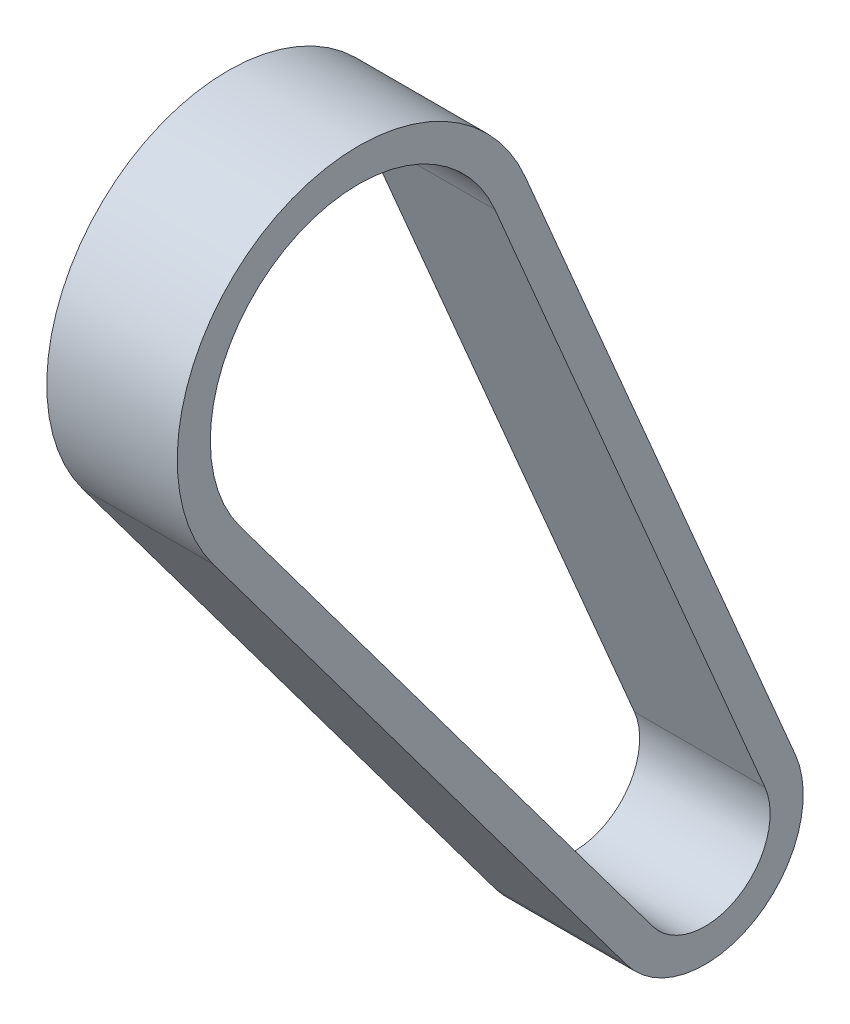
SolidWorks part; units mm, degrees
ref_plane "Alzado" through (0, 0, 0) normal (0, 0, 1) x (1, 0, 0)
ref_plane "Planta" through (0, 0, 0) normal (0, 1, 0) x (1, 0, 0)
ref_plane "Vista lateral" through (0, 0, 0) normal (1, 0, 0) x (0, 0, -1)
sketch "Croquis1" plane through (0, 0, 0) normal (0, 1, 0) x (1, 0, 0)
  line L1 (-101.6, -12.7) -> (101.6, -12.7)
  line L2 (-101.6, -12.7) -> (-101.6, 12.7)
  line L3 (-101.6, 12.7) -> (101.6, 12.7)
  line L4 (101.6, -12.7) -> (101.6, 12.7)
  line L5 (-101.6, -12.7) -> (101.6, 12.7) construction
  line L6 (-101.6, 12.7) -> (101.6, -12.7) construction
  point P0 (0, 0)
  dimension "D1" = 25.4
  dimension "D2" = 203.2
extrude "Saliente-Extruir1" add sketch "Croquis1" along normal blind 25.4
shell "Vaciado1" thickness 3.175 removed face at (-101.6, 12.7, 0) removed face at (101.6, 12.7, 0)
sketch "Croquis2" plane through (0, 25.4, 0) normal (0, 1, 0) x (1, 0, 0)
  line L0 (101.6, 12.7) -> (-101.6, 12.7) construction
  line L1 (-25.4, -12.7) -> (25.4, -12.7)
  line L2 (-25.4, -12.7) -> (-25.4, 12.7)
  line L3 (-25.4, 12.7) -> (25.4, 12.7)
  line L4 (25.4, -12.7) -> (25.4, 12.7)
  line L5 (-25.4, -12.7) -> (25.4, 12.7) construction
  line L6 (-25.4, 12.7) -> (25.4, -12.7) construction
  line L8 (-22.225, -9.525) -> (22.225, -9.525)
  line L9 (-22.225, -9.525) -> (-22.225, 9.525)
  line L10 (-22.225, 9.525) -> (22.225, 9.525)
  line L11 (22.225, -9.525) -> (22.225, 9.525)
  line L12 (-22.225, -9.525) -> (22.225, 9.525) construction
  line L13 (-22.225, 9.525) -> (22.225, -9.525) construction
  point P0 (0, 0)
  point P8 (0, 0)
  dimension "D1" = 50.8
  dimension "D2" = 3.175
  dimension "D3" = 3.175
extrude "Saliente-Extruir2" add sketch "Croquis2" along normal blind 247.65 separate body
sketch "Croquis3" plane through (0, 25.4, 0) normal (0, 1, 0) x (1, 0, 0)
  line L0 (0, 0) -> (0, 12.7) construction
  line L1 (25.4, 12.7) -> (-25.4, 12.7) construction
  circle A0 centre (-47.625, 0) radius 3.2639
  circle A1 centre (-79.375, 0) radius 3.2639
  circle A2 centre (79.375, 0) radius 3.2639
  circle A3 centre (47.625, 0) radius 3.2639
  dimension "D1" = 47.625
  dimension "D2" = 6.5278
  dimension "D3" = 31.75
extrude "Cortar-Extruir1" cut sketch "Croquis3" against normal through all
sketch "Croquis4" plane through (0, 0, 12.7) normal (0, 0, 1) x (1, 0, 0)
  line L0 (0, 25.4) -> (0, 139.6619) construction
  line L1 (-101.6, 25.4) -> (101.6, 25.4) construction
  line L2 (0, 139.6619) -> (-23.8125, 139.6619) construction
  circle A0 centre (0, 139.6619) radius 14.3129
  circle A1 centre (0, 139.6619) radius 23.8125 construction
  circle A2 centre (-23.8125, 139.6619) radius 2.4892 construction
  circle A3 centre (-11.9062, 160.2841) radius 2.4892
  circle A4 centre (11.9063, 160.2841) radius 2.4892
  circle A5 centre (23.8125, 139.6619) radius 2.4892 construction
  circle A6 centre (11.9062, 119.0397) radius 2.4892
  circle A7 centre (-11.9063, 119.0397) radius 2.4892
  dimension "D1" = 28.6258
  dimension "D3" = 47.625
  dimension "D4" = 4.9784
  dimension "D2" = 114.2619
  dimension "D6" = 23.8125
  dimension "D5" = 6
extrude "Cortar-Extruir2" cut sketch "Croquis4" against normal through all
sketch "Croquis8" plane through (0, 0, 12.7) normal (0, 0, 1) x (1, 0, 0)
  line L0 (0, 0) -> (0, 273.05) construction
  line L1 (-101.6, 12.7) -> (0, 12.7) construction
  line L2 (-101.6, 25.4) -> (-101.6, 0) construction
  line L3 (0, 12.7) -> (-12.7, 12.7) construction
  line L4 (0, 12.7) -> (12.7, 12.7) construction
  line L5 (-25.4, 273.05) -> (25.4, 273.05) construction
  line L6 (-12.7, 12.7) -> (-12.7, 25.4) construction
  circle A0 centre (0, 12.7) radius 2.4892
  circle A1 centre (-12.7, 12.7) radius 2.4892
  circle A2 centre (-25.4, 12.7) radius 2.4892
  circle A3 centre (-38.1, 12.7) radius 2.4892
  circle A4 centre (-50.8, 12.7) radius 2.4892
  circle A5 centre (0, 12.7) radius 2.4892
  circle A6 centre (-12.7, 12.7) radius 2.4892
  circle A7 centre (-25.4, 12.7) radius 2.4892
  circle A8 centre (-38.1, 12.7) radius 2.4892
  circle A9 centre (12.7, 12.7) radius 2.4892
  circle A10 centre (0, 12.7) radius 2.4892
  circle A11 centre (-12.7, 12.7) radius 2.4892
  circle A12 centre (-25.4, 12.7) radius 2.4892
  circle A13 centre (25.4, 12.7) radius 2.4892
  circle A14 centre (12.7, 12.7) radius 2.4892
  circle A15 centre (0, 12.7) radius 2.4892
  circle A16 centre (-12.7, 12.7) radius 2.4892
  circle A17 centre (38.1, 12.7) radius 2.4892
  circle A18 centre (25.4, 12.7) radius 2.4892
  circle A19 centre (12.7, 12.7) radius 2.4892
  circle A20 centre (0, 12.7) radius 2.4892
  circle A21 centre (12.7, 12.7) radius 2.4892
  circle A22 centre (25.4, 12.7) radius 2.4892
  circle A23 centre (38.1, 12.7) radius 2.4892
  circle A24 centre (50.8, 12.7) radius 2.4892
  circle A25 centre (-12.7, 25.4) radius 2.4892 [skipped]
  circle A26 centre (12.7, 25.4) radius 2.4892 [skipped]
  circle A27 centre (-12.7, 38.1) radius 2.4892
  circle A28 centre (12.7, 38.1) radius 2.4892
  circle A29 centre (-12.7, 50.8) radius 2.4892
  circle A30 centre (12.7, 50.8) radius 2.4892
  circle A31 centre (-12.7, 63.5) radius 2.4892
  circle A32 centre (12.7, 63.5) radius 2.4892
  circle A33 centre (-12.7, 76.2) radius 2.4892
  circle A34 centre (12.7, 76.2) radius 2.4892
  dimension "D1" = 4.9784
  dimension "D4" = 12.7
  dimension "D5" = 12.7
  dimension "D7" = 12.7
  dimension "D2" = 5
  dimension "D3" = 5
  dimension "D6" = 6
extrude "Cortar-Extruir4" cut sketch "Croquis8" against normal through all contours A4 | A3 | A2 | A1 | A0 | A9 | A13 | A17 | A24 | A28 | A29 | A30 | A31 | A32 | A34 | A33 | A27 region at (0, 12.7, 12.7) region at (-12.7, 12.7, 12.7) region at (-25.4, 12.7, 12.7) region at (-38.1, 12.7, 12.7) region at (-50.8, 12.7, 12.7) region at (12.7, 12.7, 12.7) region at (25.4, 12.7, 12.7) region at (38.1, 12.7, 12.7) region at (50.8, 12.7, 12.7) region at (12.7, 38.1, 12.7) region at (-12.7, 50.8, 12.7) region at (12.7, 50.8, 12.7) region at (-12.7, 63.5, 12.7) region at (12.7, 63.5, 12.7) region at (-12.7, 76.2, 12.7) region at (12.7, 76.2, 12.7)
sketch "Croquis6" plane through (0, 0, 12.7) normal (0, 0, 1) x (1, 0, 0)
  line L0 (25.4, 273.05) -> (25.4, 25.4) construction
  line L1 (-25.4, 88.646) -> (25.4, 88.646)
  line L2 (-25.4, 88.646) -> (-25.4, 114.046)
  line L3 (-25.4, 114.046) -> (25.4, 114.046)
  line L4 (25.4, 88.646) -> (25.4, 114.046)
  line L5 (-25.4, 88.646) -> (25.4, 114.046) construction
  line L6 (-25.4, 114.046) -> (25.4, 88.646) construction
  line L7 (-101.6, 25.4) -> (101.6, 25.4) construction
  line L9 (-22.225, 91.821) -> (22.225, 91.821)
  line L10 (-22.225, 91.821) -> (-22.225, 110.871)
  line L11 (-22.225, 110.871) -> (22.225, 110.871)
  line L12 (22.225, 91.821) -> (22.225, 110.871)
  line L13 (-22.225, 91.821) -> (22.225, 110.871) construction
  line L14 (-22.225, 110.871) -> (22.225, 91.821) construction
  point P0 (0, 101.346)
  point P11 (0, 101.346)
  dimension "D1" = 25.4
  dimension "D2" = 63.246
  dimension "D3" = 3.175
  dimension "D4" = 3.175
extrude "Saliente-Extruir3" add sketch "Croquis6" along normal blind 69.85 separate body
sketch "Croquis7" plane through (0, 114.046, 0) normal (0, 1, 0) x (1, 0, 0)
  line L0 (0, -12.7) -> (0, -82.55) construction
  line L1 (-25.4, -12.7) -> (25.4, -12.7) construction
  line L2 (25.4, -82.55) -> (-25.4, -82.55) construction
  line L3 (16.51, -12.7) -> (-16.51, -12.7)
  line L4 (25.4, -12.7) -> (-25.4, -12.7) construction
  line L5 (-16.51, -12.7) -> (-16.51, -34.798)
  line L6 (-13.208, -38.1) -> (13.208, -38.1)
  line L7 (16.51, -12.7) -> (16.51, -34.798)
  arc A0 (16.51, -34.798) -> (13.208, -38.1) centre (13.208, -34.798) cw
  arc A1 (-16.51, -34.798) -> (-13.208, -38.1) centre (-13.208, -34.798) ccw
  point P12 (0, -38.1)
  point P16 (16.51, -38.1)
  point P19 (-16.51, -38.1)
  dimension "D3" = 3.302
  dimension "D1" = 25.4
  dimension "D2" = 33.02
extrude "Cortar-Extruir3" cut sketch "Croquis7" against normal up to next (3.175 mm away)
sketch "Croquis11" plane through (25.4, 0, 0) normal (1, 0, 0) x (0, 0, -1)
  line L0 (0, -101.854) -> (-381, -101.854) construction
  line L1 (-82.55, 88.646) -> (-82.55, 114.046) construction
  line L2 (-82.55, 88.646) -> (-12.7, 88.646) construction
  line L6 (-517.96, -101.854) -> (-276.66, -101.854) construction
  line L7 (-517.96, -101.854) -> (-517.96, 139.446) construction
  line L8 (-517.96, 139.446) -> (-276.66, 139.446) construction
  line L9 (-276.66, -101.854) -> (-276.66, 139.446) construction
  circle A0 centre (-396.875, 145.796) radius 38.1
  dimension "D3" = 76.2
  dimension "D4" = 209.55
  dimension "D5" = 276.225
  dimension "D1" = 190.5
  dimension "D2" = 381
  dimension "D6" = 241.3
sketch "Croquis9" plane through (0, 0, 12.7) normal (0, 0, 1) x (1, 0, 0)
  line L0 (0, 0) -> (0, 273.05) construction
  line L1 (-25.4, 273.05) -> (25.4, 273.05) construction
  line L2 (50.8, 0) -> (-50.8, 0)
  line L3 (-101.6, 0) -> (101.6, 0) construction
  line L4 (-57.15, 6.35) -> (-57.15, 23.7481)
  line L5 (-101.6, 25.4) -> (101.6, 25.4) construction
  line L6 (-56.3451, 26.8425) -> (-27.2168, 79.0403)
  line L7 (-25.4, 273.05) -> (-25.4, 25.4) construction
  line L8 (-21.6717, 82.296) -> (21.6717, 82.296)
  line L9 (56.3451, 26.8425) -> (27.2168, 79.0403)
  line L10 (57.15, 6.35) -> (57.15, 23.7481)
  line L11 (-25.4, 88.646) -> (25.4, 88.646) construction
  circle A0 centre (-50.8, 12.7) radius 2.4892 construction
  arc A2 (-50.8, 0) -> (-57.15, 6.35) centre (-50.8, 6.35) cw
  arc A3 (-57.15, 23.7481) -> (-56.3451, 26.8425) centre (-50.8, 23.7481) cw
  arc A4 (-27.2168, 79.0403) -> (-21.6717, 82.296) centre (-21.6717, 75.946) cw
  arc A5 (27.2168, 79.0403) -> (21.6717, 82.296) centre (21.6717, 75.946) ccw
  arc A6 (57.15, 23.7481) -> (56.3451, 26.8425) centre (50.8, 23.7481) ccw
  arc A7 (50.8, 0) -> (57.15, 6.35) centre (50.8, 6.35) ccw
  circle A9 centre (-25.4, 12.7) radius 2.4892
  circle A10 centre (-25.4, 12.7) radius 2.4892
  circle A11 centre (-12.7, 12.7) radius 2.4892
  circle A12 centre (-12.7, 12.7) radius 2.4892
  circle A13 centre (0, 12.7) radius 2.4892
  circle A14 centre (0, 12.7) radius 2.4892
  circle A15 centre (0, 12.7) radius 2.4892
  circle A16 centre (0, 12.7) radius 2.4892
  circle A17 centre (12.7, 12.7) radius 2.4892
  circle A18 centre (12.7, 12.7) radius 2.4892
  circle A19 centre (-38.1, 12.7) radius 2.4892
  circle A20 centre (-38.1, 12.7) radius 2.4892
  circle A21 centre (-25.4, 12.7) radius 2.4892
  circle A22 centre (-25.4, 12.7) radius 2.4892
  circle A23 centre (-12.7, 12.7) radius 2.4892
  circle A24 centre (-12.7, 12.7) radius 2.4892
  circle A25 centre (0, 12.7) radius 2.4892
  circle A26 centre (0, 12.7) radius 2.4892
  circle A27 centre (-50.8, 12.7) radius 2.4892
  circle A28 centre (-50.8, 12.7) radius 2.4892
  circle A29 centre (-38.1, 12.7) radius 2.4892
  circle A30 centre (-38.1, 12.7) radius 2.4892
  circle A31 centre (25.4, 12.7) radius 2.4892
  circle A32 centre (25.4, 12.7) radius 2.4892
  circle A33 centre (38.1, 12.7) radius 2.4892
  circle A34 centre (38.1, 12.7) radius 2.4892
  circle A35 centre (-12.7, 12.7) radius 2.4892
  circle A36 centre (-12.7, 12.7) radius 2.4892
  circle A37 centre (0, 12.7) radius 2.4892
  circle A38 centre (0, 12.7) radius 2.4892
  circle A39 centre (12.7, 12.7) radius 2.4892
  circle A40 centre (12.7, 12.7) radius 2.4892
  circle A41 centre (25.4, 12.7) radius 2.4892
  circle A42 centre (25.4, 12.7) radius 2.4892
  circle A43 centre (-25.4, 12.7) radius 2.4892
  circle A44 centre (-25.4, 12.7) radius 2.4892
  circle A45 centre (-12.7, 12.7) radius 2.4892
  circle A46 centre (-12.7, 12.7) radius 2.4892
  circle A47 centre (50.8, 12.7) radius 2.4892
  circle A48 centre (50.8, 12.7) radius 2.4892
  circle A49 centre (38.1, 12.7) radius 2.4892
  circle A50 centre (38.1, 12.7) radius 2.4892
  circle A51 centre (25.4, 12.7) radius 2.4892
  circle A52 centre (25.4, 12.7) radius 2.4892
  circle A53 centre (12.7, 12.7) radius 2.4892
  circle A54 centre (12.7, 12.7) radius 2.4892
  circle A55 centre (0, 12.7) radius 2.4892
  circle A56 centre (0, 12.7) radius 2.4892
  circle A57 centre (12.7, 12.7) radius 2.4892
  circle A58 centre (12.7, 12.7) radius 2.4892
  circle A59 centre (-12.7, 76.2) radius 2.4892
  circle A60 centre (-12.7, 76.2) radius 2.4892
  circle A61 centre (12.7, 63.5) radius 2.4892
  circle A62 centre (12.7, 63.5) radius 2.4892
  circle A63 centre (-12.7, 63.5) radius 2.4892
  circle A64 centre (-12.7, 63.5) radius 2.4892
  circle A65 centre (12.7, 50.8) radius 2.4892
  circle A66 centre (12.7, 50.8) radius 2.4892
  circle A67 centre (-12.7, 50.8) radius 2.4892
  circle A68 centre (-12.7, 50.8) radius 2.4892
  circle A69 centre (12.7, 38.1) radius 2.4892
  circle A70 centre (12.7, 38.1) radius 2.4892
  circle A71 centre (-12.7, 38.1) radius 2.4892
  circle A72 centre (-12.7, 38.1) radius 2.4892
  circle A73 centre (12.7, 76.2) radius 2.4892
  circle A74 centre (12.7, 76.2) radius 2.4892
  point P22 (-57.15, 0)
  point P25 (-57.15, 25.4)
  point P28 (-25.4, 82.296)
  point P38 (0, 82.296)
  circle M37 centre (-50.8, 12.7) radius 2.4892
  circle M38 centre (-38.1, 12.7) radius 2.4892
  circle M39 centre (-25.4, 12.7) radius 2.4892
  circle M40 centre (-12.7, 12.7) radius 2.4892
  circle M41 centre (0, 12.7) radius 2.4892
  circle M42 centre (12.7, 12.7) radius 2.4892
  circle M43 centre (25.4, 12.7) radius 2.4892
  circle M44 centre (38.1, 12.7) radius 2.4892
  circle M45 centre (50.8, 12.7) radius 2.4892
  line M46 (-101.6, 0) -> (101.6, 0)
  line M48 (101.6, 25.4) -> (-101.6, 25.4)
  dimension "D1" = 6.35
  dimension "D3" = 6.35
  dimension "D37" = 6.35
  dimension "D4" = 0
  dimension "D5" = 0
  dimension "D6" = 0
  dimension "D7" = 0
  dimension "D8" = 0
  dimension "D9" = 0
  dimension "D10" = 0
  dimension "D11" = 0
  dimension "D12" = 0
  dimension "D13" = 0
  dimension "D14" = 0
  dimension "D15" = 0
  dimension "D16" = 0
  dimension "D17" = 0
  dimension "D18" = 0
  dimension "D19" = 0
  dimension "D20" = 0
  dimension "D21" = 0
  dimension "D22" = 0
  dimension "D23" = 0
  dimension "D24" = 0
  dimension "D25" = 0
  dimension "D26" = 0
  dimension "D27" = 0
  dimension "D28" = 0
  dimension "D29" = 0
  dimension "D30" = 0
  dimension "D31" = 0
  dimension "D32" = 0
  dimension "D33" = 0
  dimension "D34" = 0
  dimension "D35" = 0
  dimension "D36" = 0
extrude "Saliente-Extruir4" add sketch "Croquis9" along normal blind 6.35 separate body contours L0 L8 A4 L6 A3 A60 A64 A68 A72 M48 | L0 A6 L9 A5 L8 A74 A70 A66 A62 M48 | L0 A3 L4 A2 M46 M41 M48 M37 M39 M40 M38 | L0 L2 A7 L10 A6 A56 M48 M42 M44 M45 M43 region at (-28.4143, 12.7709, 12.7) region at (28.4143, 12.7709, 12.7) region at (-21.9575, 49.932, 12.7) region at (21.9575, 49.932, 12.7)
sketch "Croquis15" plane through (25.4, 0, 0) normal (1, 0, 0) x (0, 0, -1)
  line L0 (-12.7, 0) -> (-12.7, 171.1325) construction
  line L1 (-12.7, 273.05) -> (-12.7, 25.4) construction
  line L2 (-72.5746, 227.1642) -> (-41.5317, 154.1315) construction
  line L3 (-105.4538, 208.2656) -> (-57.9713, 144.6822) construction
  line L4 (-94.6246, 238.2605) -> (-401.3483, 164.3633) construction
  line L5 (-392.4017, 127.2287) -> (-85.6779, 201.1258) construction
  line L8 (-82.55, 114.046) -> (-12.7, 114.046) construction
  circle A0 centre (-50.32, 150.396) radius 30
  arc A1 (-57.9713, 144.6822) -> (-41.5317, 154.1315) centre (-50.32, 150.396) ccw construction
  arc A2 (-401.3483, 164.3633) -> (-392.4017, 127.2287) centre (-396.875, 145.796) ccw construction
  arc A3 (-72.5746, 227.1642) -> (-105.4538, 208.2656) centre (-90.1513, 219.6932) ccw construction
  arc A4 (-85.6779, 201.1258) -> (-94.6246, 238.2605) centre (-90.1513, 219.6932) ccw construction
  dimension "D2" = 60
  dimension "D3" = 19.0986
  dimension "D4" = 38.1972
  dimension "D1" = 171.1325
  dimension "D7" = 6.35
  dimension "D8" = 7.62
sketch "Croquis16" plane through (25.4, 0, 0) normal (1, 0, 0) x (0, 0, -1)
  line L0 (-50.32, 150.396) -> (-50.32, 175.796) construction
  line L1 (-13.4332, 272.8734) -> (-118.1525, 247.644)
  line L2 (-82.55, 94.996) -> (-82.55, 113.9625)
  line L3 (-82.5522, 114.1295) -> (-83.4835, 149.5234)
  line L4 (-76.2, 88.646) -> (6.35, 88.646)
  line L5 (12.7, 273.05) -> (12.7, 25.4) construction
  line L6 (12.7, 94.996) -> (12.7, 266.7)
  line L7 (6.35, 273.05) -> (-11.9459, 273.05)
  line L8 (-94.6246, 238.2605) -> (-401.3483, 164.3633) construction
  line L9 (-122.8385, 239.9833) -> (-110.0117, 186.743)
  line L10 (-90.1513, 219.6932) -> (-116.4251, 213.3632) construction
  circle A0 centre (-90.1513, 219.6932) radius 14.3256
  circle A1 centre (-50.32, 150.396) radius 33.175
  circle A4 centre (-50.32, 150.396) radius 9.5631
  circle A5 centre (-50.32, 150.396) radius 25.4 construction
  circle A6 centre (-50.32, 175.796) radius 2.4892
  circle A7 centre (-32.3595, 168.3565) radius 2.4892 construction
  circle A8 centre (-24.92, 150.396) radius 2.4892
  circle A9 centre (-32.3595, 132.4355) radius 2.4892
  circle A10 centre (-50.32, 124.996) radius 2.4892
  circle A11 centre (-68.2805, 132.4355) radius 2.4892
  circle A12 centre (-75.72, 150.396) radius 2.4892
  circle A13 centre (-68.2805, 168.3565) radius 2.4892
  arc A18 (-105.7366, 182.1707) -> (-83.4864, 151.1506) centre (-115.2282, 151.8727) cw
  arc A19 (-110.0117, 186.743) -> (-105.7366, 182.1707) centre (-103.8383, 188.2304) ccw
  arc A21 (-118.1525, 247.644) -> (-122.8385, 239.9833) centre (-116.6652, 241.4706) ccw
  arc A23 (-11.9459, 273.05) -> (-13.4332, 272.8734) centre (-11.9459, 266.7) ccw
  circle A26 centre (-50.32, 150.396) radius 30 construction
  arc A29 (-82.55, 113.9625) -> (-82.5522, 114.1295) centre (-88.9, 113.9625) ccw
  arc A31 (12.7, 266.7) -> (6.35, 273.05) centre (6.35, 266.7) ccw
  arc A32 (6.35, 88.646) -> (12.7, 94.996) centre (6.35, 94.996) ccw
  arc A33 (-82.55, 94.996) -> (-76.2, 88.646) centre (-76.2, 94.996) ccw
  point P45 (-12.7, 273.05)
  point P72 (-82.55, 114.046)
  point P74 (12.7, 273.05)
  point P77 (12.7, 88.646)
  point P80 (-82.55, 88.646)
  line M2 (12.7, 25.4) -> (12.7, 273.05)
  line M3 (12.7, 273.05) -> (-12.7, 273.05)
  line M4 (-12.7, 273.05) -> (-12.7, 25.4)
  dimension "D1" = 28.6512
  dimension "D2" = 3.175
  dimension "D3" = 31.75
  dimension "D4" = 19.1262
  dimension "D5" = 50.8
  dimension "D6" = 4.9784
  dimension "D9" = 6.35
  dimension "D10" = 6.35
  dimension "D14" = 6.35
  dimension "D15" = 6.35
  dimension "D12" = 6.35
  dimension "D8" = 25.4
  dimension "D11" = 12.7
  dimension "D7" = 8
extrude "Saliente-Extruir5" add sketch "Croquis16" along normal blind 6.35 separate body contours L4 A32 A31 A23 M2 M3 M4 | L2 A33 L4 A23 L1 A21 L9 A19 A18 A1 L3 A29 A0 M4 | A1 A13 A12 A11 A10 A9 A8 A6 A4 region at (25.4, 191.9467, 55.8371) region at (25.4, 180.8478, 0.0418) region at (25.4, 182.6306, 49.9534)
sketch "Croquis12" plane through (25.4, 0, 0) normal (1, 0, 0) x (0, 0, -1)
  line L0 (-82.55, 101.346) -> (-12.7, 101.346) construction
  line L1 (-82.55, 88.646) -> (-82.55, 114.046) construction
  line L2 (-12.7, 88.646) -> (-12.7, 114.046) construction
  line L3 (0, 273.05) -> (0, 0) construction
  line L4 (-12.7, 273.05) -> (12.7, 273.05) construction
  line L5 (0, 101.346) -> (-12.7, 101.346) construction
  line L6 (0, 101.346) -> (0, 114.046) construction
  circle A1 centre (0, 101.346) radius 2.4892
  circle A2 centre (-12.7, 101.346) radius 2.4892 [skipped]
  circle A3 centre (-25.4, 101.346) radius 2.4892
  circle A4 centre (-38.1, 101.346) radius 2.4892
  circle A5 centre (-50.8, 101.346) radius 2.4892
  circle A6 centre (0, 114.046) radius 2.4892
  circle A7 centre (0, 126.746) radius 2.4892
  circle A8 centre (0, 139.446) radius 2.4892
  circle A9 centre (0, 152.146) radius 2.4892
  circle A10 centre (0, 164.846) radius 2.4892
  circle A11 centre (0, 177.546) radius 2.4892
  circle A12 centre (0, 190.246) radius 2.4892
  circle A13 centre (0, 202.946) radius 2.4892
  circle A14 centre (0, 215.646) radius 2.4892
  circle A15 centre (0, 228.346) radius 2.4892
  circle A16 centre (0, 241.046) radius 2.4892
  circle A17 centre (0, 253.746) radius 2.4892
  circle A18 centre (0, 266.446) radius 2.4892
  circle A19 centre (-63.5, 101.346) radius 2.4892
  circle A20 centre (-76.2, 101.346) radius 2.4892
  dimension "D1" = 4.9784
  dimension "D3" = 12.7
  dimension "D5" = 12.7
  dimension "D2" = 7
  dimension "D4" = 14
extrude "Cortar-Extruir5" cut sketch "Croquis12" against normal through all and the other way through all
sketch "Croquis17" plane through (31.75, 0, 0) normal (1, 0, 0) x (0, 0, -1)
  line L0 (-403.5186, 170.3118) -> (-118.2389, 247.6205)
  line L1 (-118.0654, 247.6649) -> (-21.2705, 270.9852)
  line L2 (-390.9258, 121.1026) -> (-118.1525, 186.8202)
  line L3 (-392.4017, 127.2287) -> (-85.6779, 201.1258) construction
  line L4 (-118.1525, 186.8202) -> (-112.4025, 188.2055)
  line L5 (-13.4332, 206.3797) -> (-13.4332, 264.8118)
  line L7 (-403.3993, 184.1476) -> (-418.6226, 158.9186)
  circle A0 centre (-396.875, 145.796) radius 14.3256
  circle A1 centre (-90.1513, 219.6932) radius 14.3256
  circle A2 centre (-396.875, 145.796) radius 25.4
  arc A3 (-118.2389, 247.6205) -> (-118.0654, 247.6649) centre (-116.578, 241.4916) cw
  arc A4 (-21.2705, 270.9852) -> (-13.4332, 264.8118) centre (-19.7832, 264.8118) cw
  arc A5 (-13.4332, 206.3797) -> (-43.9384, 181.4981) centre (-38.8332, 206.3797) cw
  circle A6 centre (-50.32, 150.396) radius 31.75
  arc A8 (-110.0117, 186.743) -> (-105.7366, 182.1707) centre (-103.8383, 188.2304) ccw construction
  arc A9 (-110.0117, 186.743) -> (-105.7366, 182.1707) centre (-103.8383, 188.2304) ccw
  arc A10 (-110.0117, 186.743) -> (-112.4025, 188.2055) centre (-111.9383, 186.2789) ccw
  arc A11 (-83.4864, 151.1506) -> (-105.7366, 182.1707) centre (-115.2282, 151.8727) ccw construction
  arc A12 (-89.8175, 170.9084) -> (-105.7366, 182.1707) centre (-115.2282, 151.8727) ccw
  arc A13 (-89.8175, 170.9084) -> (-74.8387, 170.5677) centre (-82.1943, 176.6192) ccw
  circle A14 centre (-396.875, 180.2108) radius 7.62
  arc A16 (-389.8471, 183.1558) -> (-377.8191, 177.2761) centre (-380.4766, 187.0824) ccw
  point P19 (-118.1525, 247.644)
  point P23 (-13.4332, 272.8734)
  line M28 (-13.4332, 272.8734) -> (-118.1525, 247.644)
  arc M29 (-118.1525, 247.644) -> (-122.8385, 239.9833) centre (-116.6652, 241.4706) ccw
  line M30 (-122.8385, 239.9833) -> (-110.0117, 186.743)
  circle M38 centre (-90.1513, 219.6932) radius 14.3256
  dimension "D1" = 28.6512
  dimension "D2" = 50.8
  dimension "D3" = 6.35
  dimension "D4" = 63.5
  dimension "D5" = 9.525
  dimension "D6" = 25.4
  dimension "D7" = 15.24
  dimension "D8" = 34.4148
  dimension "D9" = 10.16
extrude "Saliente-Extruir6" add sketch "Croquis17" along normal blind 6.35 separate body contours A2 L2 L0 M30 M29 | L5 A4 A3 L0 M28 M29 M30 M38 | A2 A0 | A16 A14 L7 A2 L0 | A14 M30 region at (31.75, 173.536, 401.4081) region at (31.75, 184.8147, 244.5216) region at (31.75, 165.3985, 381.8776) region at (31.75, 220.7032, 61.6214) region at (31.75, 180.2108, 396.875)
sketch "Croquis18" plane through (38.1, 0, 0) normal (1, 0, 0) x (0, 0, -1)
  line L0 (-122.8385, 239.9833) -> (-110.0117, 186.743) construction
  line L1 (-122.754, 239.6323) -> (-111.9631, 194.8431)
  line L2 (-403.5186, 170.3118) -> (-118.2389, 247.6205) construction
  line L3 (-403.3993, 184.1476) -> (-418.6226, 158.9186) construction
  line L5 (-403.3993, 184.1476) -> (-418.6226, 158.9186)
  line L6 (-390.9258, 121.1026) -> (-118.1525, 186.8202) construction
  line L7 (-403.5186, 170.3118) -> (-130.5882, 244.274)
  line L10 (-122.8385, 239.9833) -> (-110.0117, 186.743) construction
  line L11 (-390.9258, 121.1026) -> (-116.6492, 187.1824)
  circle A1 centre (-396.875, 145.796) radius 25.4
  circle A2 centre (-396.875, 145.796) radius 25.4
  arc A3 (-116.6492, 187.1824) -> (-111.9631, 194.8431) centre (-118.1365, 193.3558) ccw
  circle A5 centre (-396.875, 145.796) radius 14.3256
  circle A6 centre (-396.875, 145.796) radius 14.3256
  arc A12 (-122.754, 239.6323) -> (-130.5882, 244.274) centre (-128.9273, 238.145) ccw
  arc A13 (-389.8471, 183.1558) -> (-377.8191, 177.2761) centre (-380.4766, 187.0824) ccw construction
  circle A14 centre (-396.875, 180.2108) radius 7.62 construction
  arc A15 (-389.8471, 183.1558) -> (-377.8191, 177.2761) centre (-380.4766, 187.0824) ccw
  circle A16 centre (-396.875, 180.2108) radius 7.62
  point P18 (-110.4758, 188.6697)
  line M10 (-118.2389, 247.6205) -> (-377.8191, 177.2761)
  arc M11 (-418.6226, 158.9186) -> (-390.9258, 121.1026) centre (-396.875, 145.796) ccw
  circle M13 centre (-396.875, 145.796) radius 14.3256
  line M33 (-403.3993, 184.1476) -> (-418.6226, 158.9186)
  arc M34 (-377.8191, 177.2761) -> (-389.8471, 183.1558) centre (-380.4766, 187.0824) cw
  arc M35 (-389.8471, 183.1558) -> (-403.3993, 184.1476) centre (-396.875, 180.2108) ccw
  dimension "D2" = 6.35
  dimension "D1" = 0
  dimension "D3" = 0
extrude "Saliente-Extruir7" add sketch "Croquis18" along normal blind 6.35 from surface separate body contours L1 A12 A2 A3 M10 | A2 M11 M13 | A16 A2 L7 M33 M34 | A16 M35 region at (38.1, 184.7417, 244.7476) region at (38.1, 173.536, 401.4081) region at (38.1, 131.2122, 416.7871) region at (38.1, 180.2108, 396.875) starting at face at (25.4, 101.346, -2.4892)
sketch "Croquis22" plane through (38.1, 0, 0) normal (1, 0, 0) x (0, 0, -1)
  line L0 (-396.875, 145.796) -> (-90.1513, 219.6932) construction
  line L1 (-90.1513, 219.6932) -> (-50.32, 150.396) construction
  line L4 (-50.32, 236.121) -> (-37.62, 236.121) construction
  line L5 (-21.2705, 270.9852) -> (-118.0654, 247.6649) construction
  circle A0 centre (-396.875, 180.2108) radius 3.2639
  circle A1 centre (-364.7735, 153.53) radius 3.2639
  circle A2 centre (-396.875, 145.796) radius 19.0986 construction
  arc A3 (-401.3483, 164.3633) -> (-392.4017, 127.2287) centre (-396.875, 145.796) ccw construction
  circle A4 centre (-364.7735, 153.53) radius 6.35 construction
  circle A7 centre (-72.747, 189.4137) radius 3.2639
  circle A8 centre (-72.747, 189.4137) radius 6.35 construction
  circle A9 centre (-50.32, 213.896) radius 6.35 construction
  circle A10 centre (-50.32, 213.896) radius 3.2639
  circle A13 centre (-37.62, 236.121) radius 3.2639
  circle A14 centre (-37.62, 236.121) radius 6.35 construction
  circle A15 centre (-72.747, 252.0515) radius 3.2639
  circle A16 centre (-72.747, 252.0515) radius 6.35 construction
  circle A17 centre (-19.7832, 264.8118) radius 6.35 construction
  circle A18 centre (-19.7832, 264.8118) radius 3.2639
  dimension "D1" = 6.5278
  dimension "D2" = 33.02
  dimension "D3" = 12.7
  dimension "D4" = 34.925
  dimension "D5" = 63.5
  dimension "D6" = 22.225
  dimension "D7" = 12.7
extrude "Cortar-Extruir6" cut sketch "Croquis22" against normal through all
sketch "Croquis24" plane through (38.1, 0, 0) normal (1, 0, 0) x (0, 0, -1)
  line L0 (-396.875, 145.796) -> (-90.1513, 219.6932) construction
  line L1 (-243.5131, 182.7446) -> (-247.9864, 201.3119) construction
  line L2 (-94.6246, 238.2605) -> (-401.3483, 164.3633) construction
  circle A0 centre (-295.9867, 170.1024) radius 2.4892
  circle A1 centre (-191.0395, 195.3867) radius 2.4892
  dimension "D1" = 4.9784
  dimension "D2" = 53.975
extrude "Cortar-Extruir7" cut sketch "Croquis24" against normal through all
sketch "Croquis25" plane through (31.75, 0, 0) normal (1, 0, 0) x (0, 0, -1)
  line L0 (-12.7, 0) -> (-12.7, 139.7) construction
  line L1 (-12.7, 123.825) -> (-12.7, 155.575)
  line L2 (-12.7, 0) -> (-12.7, 171.1325) construction
  line L3 (-15.875, 158.75) -> (-17.145, 158.75)
  line L4 (-20.32, 155.575) -> (-20.32, 123.825)
  line L5 (-12.7, 139.7) -> (-20.32, 139.7) construction
  line L6 (-15.875, 120.65) -> (-17.145, 120.65)
  arc A0 (-12.7, 155.575) -> (-15.875, 158.75) centre (-15.875, 155.575) ccw
  arc A1 (-15.875, 120.65) -> (-12.7, 123.825) centre (-15.875, 123.825) ccw
  arc A2 (-17.145, 120.65) -> (-20.32, 123.825) centre (-17.145, 123.825) cw
  arc A3 (-17.145, 158.75) -> (-20.32, 155.575) centre (-17.145, 155.575) ccw
  point P13 (-12.7, 158.75)
  point P16 (-12.7, 120.65)
  point P19 (-20.32, 120.65)
  point P22 (-20.32, 158.75)
  dimension "D4" = 3.175
  dimension "D1" = 139.7
  dimension "D2" = 7.62
  dimension "D3" = 38.1
extrude "Cortar-Extruir8" cut sketch "Croquis25" against normal through all
delete or keep bodies "Sólido-Eliminar/Conservar 1" [suppressed] type keep bodies bodies 112
delete or keep bodies "Sólido-Eliminar/Conservar 2" [suppressed] type keep bodies bodies 111
delete or keep bodies "Sólido-Eliminar/Conservar 3" [suppressed] type keep bodies bodies 107
delete or keep bodies "Sólido-Eliminar/Conservar 4" [suppressed] type keep bodies bodies 109
delete or keep bodies "Sólido-Eliminar/Conservar 5" [suppressed] type keep bodies bodies 121
delete or keep bodies "Sólido-Eliminar/Conservar 6" [suppressed] type keep bodies bodies 119
sketch "Croquis29" plane through (0, 0, 0) normal (1, 0, 0) x (0, 0, -1)
  line L0 (-392.4017, 127.2287) -> (-85.6779, 201.1258) construction
  line L1 (-94.6246, 238.2605) -> (-401.3483, 164.3633) construction
  line L2 (-392.4017, 127.2287) -> (-85.6779, 201.1258) construction
  line L3 (-94.6246, 238.2605) -> (-401.3483, 164.3633) construction
  line L4 (-392.8842, 129.2314) -> (-86.1604, 203.1285)
  line L5 (-94.1421, 236.2578) -> (-400.8658, 162.3606)
  line L6 (-391.9941, 125.5371) -> (-85.2704, 199.4342)
  line L7 (-95.0321, 239.9521) -> (-401.7559, 166.0549)
  arc A0 (-85.6779, 201.1258) -> (-94.6246, 238.2605) centre (-90.1513, 219.6932) ccw construction
  arc A1 (-401.3483, 164.3633) -> (-392.4017, 127.2287) centre (-396.875, 145.796) ccw construction
  arc A2 (-85.6779, 201.1258) -> (-94.6246, 238.2605) centre (-90.1513, 219.6932) ccw construction
  arc A3 (-401.3483, 164.3633) -> (-392.4017, 127.2287) centre (-396.875, 145.796) ccw construction
  arc A4 (-86.1604, 203.1285) -> (-94.1421, 236.2578) centre (-90.1513, 219.6932) ccw
  arc A5 (-400.8658, 162.3606) -> (-392.8842, 129.2314) centre (-396.875, 145.796) ccw
  arc A6 (-401.7559, 166.0549) -> (-391.9941, 125.5371) centre (-396.875, 145.796) ccw
  arc A7 (-85.2704, 199.4342) -> (-95.0321, 239.9521) centre (-90.1513, 219.6932) ccw
  dimension "D1" = 2.06
  dimension "D2" = 3.8
extrude "Saliente-Extruir9" add sketch "Croquis29" along normal mid plane 9 separate body
sketch "Croquis30" plane through (0, 0, 0) normal (1, 0, 0) x (0, 0, -1)
  line L0 (-72.5746, 227.1642) -> (-41.5317, 154.1315) construction
  line L1 (-105.4538, 208.2656) -> (-57.9713, 144.6822) construction
  line L2 (-72.5746, 227.1642) -> (-41.5317, 154.1315) construction
  line L3 (-105.4538, 208.2656) -> (-57.9713, 144.6822) construction
  line L4 (-74.4704, 226.3584) -> (-43.4275, 153.3257)
  line L5 (-103.8032, 209.4982) -> (-56.3207, 145.9148)
  line L6 (-106.8479, 207.2245) -> (-59.3654, 143.6411)
  line L7 (-70.9732, 227.8449) -> (-39.9303, 154.8122)
  arc A0 (-57.9713, 144.6822) -> (-41.5317, 154.1315) centre (-50.32, 150.396) ccw construction
  arc A1 (-72.5746, 227.1642) -> (-105.4538, 208.2656) centre (-90.1513, 219.6932) ccw construction
  arc A2 (-57.9713, 144.6822) -> (-41.5317, 154.1315) centre (-50.32, 150.396) ccw construction
  arc A3 (-72.5746, 227.1642) -> (-105.4538, 208.2656) centre (-90.1513, 219.6932) ccw construction
  arc A4 (-56.3207, 145.9148) -> (-43.4275, 153.3257) centre (-50.32, 150.396) ccw
  arc A5 (-74.4704, 226.3584) -> (-103.8032, 209.4982) centre (-90.1513, 219.6932) ccw
  arc A6 (-70.9732, 227.8449) -> (-106.8479, 207.2245) centre (-90.1513, 219.6932) ccw
  arc A7 (-59.3654, 143.6411) -> (-39.9303, 154.8122) centre (-50.32, 150.396) ccw
  dimension "D1" = 2.06
  dimension "D2" = 3.8
extrude "Saliente-Extruir10" add sketch "Croquis30" along normal mid plane 15 separate body
delete or keep bodies "Sólido-Eliminar/Conservar 7" [suppressed] type keep bodies bodies 123
delete or keep bodies "Sólido-Eliminar/Conservar 8" type keep bodies bodies 124
equation "\"D1@Croquis15\"=5.5500+1.1875pulgadas"
equation "\"D3@Croquis15\"=(12*5mm)/pi"
equation "\"D4@Croquis15\"=(24*5mm)/pi"
equation "\"D5@Croquis15\"=(50*5mm)+1mm"
equation "\"D6@Croquis15\"=(150*5mm)+1mm"
